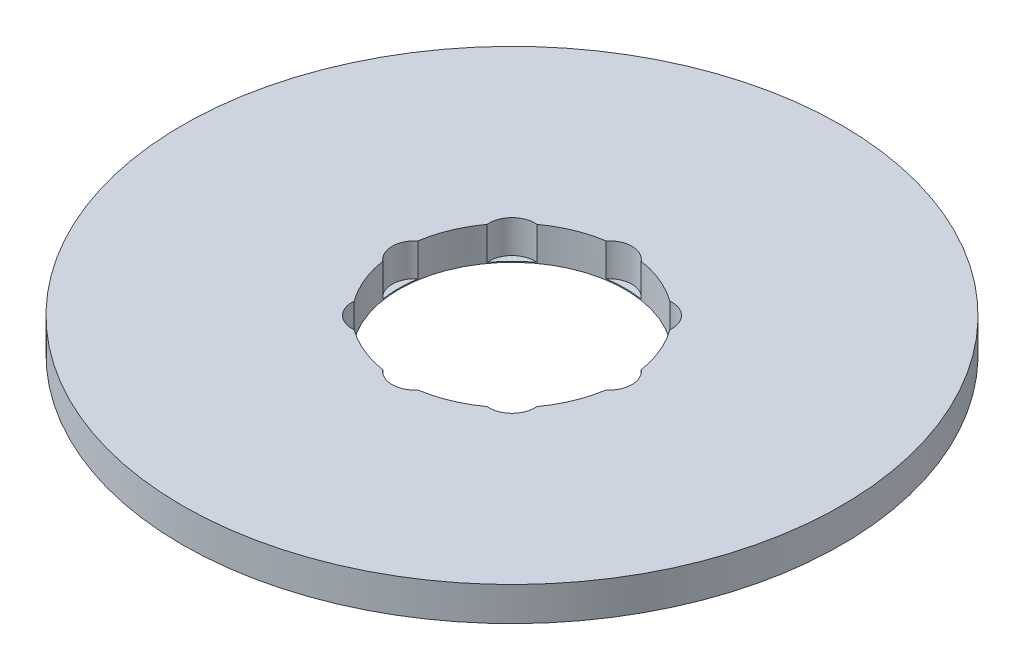
SolidWorks part; units mm, degrees
ref_plane "Front Plane" through (0, 0, 0) normal (0, 0, 1) x (1, 0, 0)
ref_plane "Top Plane" through (0, 0, 0) normal (0, 1, 0) x (1, 0, 0)
ref_plane "Right Plane" through (0, 0, 0) normal (1, 0, 0) x (0, 0, -1)
sketch "Sketch1" plane through (0, 0, 0) normal (0, 1, 0) x (1, 0, 0)
  circle A0 centre (0, 0) radius 87.5
  dimension "FLANGE_OD" = 175
extrude "Boss-Extrude1" add sketch "Sketch1" along normal blind 9
sketch "Sketch2" plane through (0, 0, 0) normal (0, 1, 0) x (1, 0, 0)
  circle A0 centre (0, 0) radius 30
  dimension "BORE_D" = 60
extrude "Cut-Extrude1" cut sketch "Sketch2" along normal through all
sketch "Sketch3" plane through (0, 9, 0) normal (0, 1, 0) x (1, 0, 0)
  circle A0 centre (0, 0) radius 25.739 construction
  circle A1 centre (-25.739, 0) radius 6.0832
  dimension "BOLT_D" = 12.1663
  dimension "BOLT_PCD" = 51.478
extrude "Cut-Extrude2" cut sketch "Sketch3" against normal blind 8.7338
pattern_circular "CirPattern1" count 8 over 360 about axis through (0, 0, 0) along (0, 1, 0) of "Cut-Extrude2"
